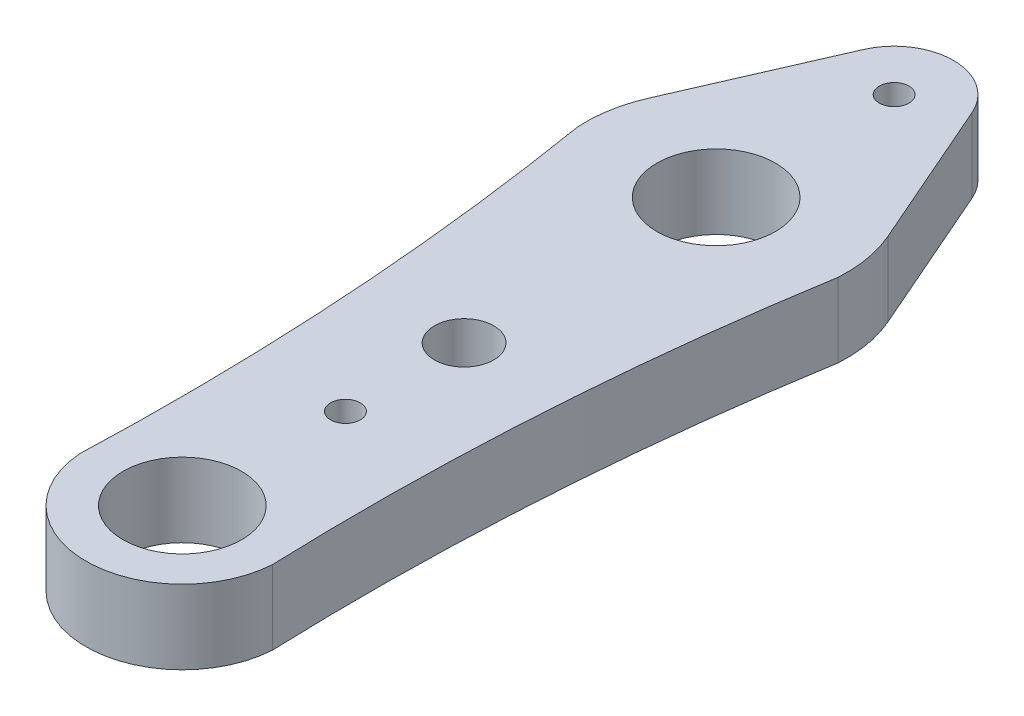
SolidWorks part; units mm, degrees
ref_plane "Front Plane" through (0, 0, 0) normal (0, 0, 1) x (1, 0, 0)
ref_plane "Top Plane" through (0, 0, 0) normal (0, 1, 0) x (1, 0, 0)
ref_plane "Right Plane" through (0, 0, 0) normal (1, 0, 0) x (0, 0, -1)
sketch "Sketch1" plane through (0, 0, 0) normal (0, 1, 0) x (1, 0, 0)
  line L0 (110.4288, 432.0143) -> (849.0954, 432.0143) construction
  line L4 (-8.0653, 20.52) -> (-3.6661, 30.6)
  line L5 (3.6661, 30.6) -> (8.0653, 20.52)
  circle A0 centre (0, 0) radius 2
  circle A1 centre (0, 17) radius 4
  circle A2 centre (0, -19) radius 4
  arc A3 (-6.446, -18.1636) -> (6.446, -18.1636) centre (0, -19) ccw
  arc A4 (8.5164, 14.7841) -> (8.0653, 20.52) centre (0, 17) ccw
  circle A6 centre (0, 29) radius 1
  arc A7 (-8.782, 16.4378) -> (-6.4867, -19.4153) centre (-186.3699, -12.9313) cw
  arc A8 (8.782, 16.4378) -> (6.4867, -19.4153) centre (186.3699, -12.9313) ccw
  arc A9 (-8.0653, 20.52) -> (-8.5164, 14.7841) centre (0, 17) ccw
  arc A10 (3.6661, 30.6) -> (-3.6661, 30.6) centre (0, 29) ccw
  circle A11 centre (0, -8) radius 1
  dimension "D1" = 4
  dimension "D4" = 8
  dimension "D5" = 8
  dimension "D6" = 13
  dimension "D7" = 17.6
  dimension "D9" = 11
  dimension "D10" = 2
  dimension "D11" = 2
  dimension "D2" = 17
  dimension "D3" = 19
  dimension "D8" = 12
extrude "Boss-Extrude1" add sketch "Sketch1" along normal blind 5 contours L5 A10 L4 A9 A7 A3 A8 A4 A11 A0 A1 A2 A6 region at (0, 0, -4.7555)
